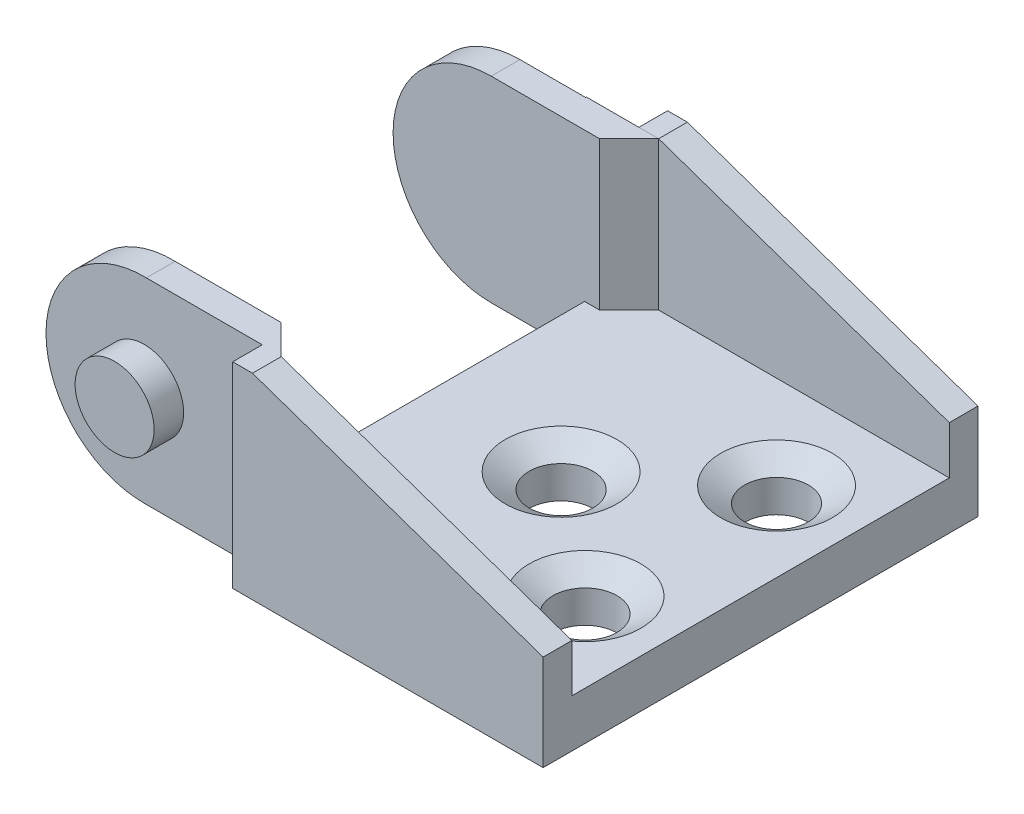
SolidWorks part; units mm, degrees
ref_plane "Front Plane" through (0, 0, 0) normal (0, 0, 1) x (1, 0, 0)
ref_plane "Top Plane" through (0, 0, 0) normal (0, 1, 0) x (1, 0, 0)
ref_plane "Right Plane" through (0, 0, 0) normal (1, 0, 0) x (0, 0, -1)
sketch "Sketch1" plane through (0, 0, 0) normal (1, 0, 0) x (0, 0, -1)
  line L0 (0, 12.3) -> (0, 0)
  line L1 (0, 0) -> (27.25, 0)
  line L2 (27.25, 0) -> (27.25, 12.3)
  line L3 (27.25, 12.3) -> (25.45, 12.3)
  line L4 (25.45, 12.3) -> (25.45, 3)
  line L5 (25.45, 3) -> (1.8, 3)
  line L6 (1.8, 3) -> (1.8, 12.3)
  line L7 (1.8, 12.3) -> (0, 12.3)
  dimension "D1" = 27.25
  dimension "D2" = 1.8
  dimension "D4" = 12.3
extrude "ProfileBoss-Extrude1" add sketch "Sketch1" along normal blind 33
sketch "Sketch2" plane through (0, 0, 0) normal (0, 0, 1) x (1, 0, 0)
  line L1 (14.7896, 12.3) -> (33, 6)
  line L2 (33, 12.3) -> (0, 12.3) construction
  line L3 (0, 12.3) -> (0, 0) construction
  line L4 (33, 12.3) -> (33, 0) construction
  line L5 (33, 6) -> (33, 0)
  line L6 (33, 0) -> (6.15, 0)
  line L7 (33, 0) -> (0, 0) construction
  line L8 (6.2896, 12.2984) -> (14.7896, 12.3)
  arc A0 (6.2896, 12.2984) -> (6.15, 0) centre (6.15, 6.15) ccw
  dimension "D1" = 12.3
  dimension "D4" = 6
  dimension "D2" = 8.5
extrude "SideProfileCut-Extrude1" cut sketch "Sketch2" against normal through all flip side to cut
sketch "Sketch3" plane through (0, 3, 0) normal (0, 1, 0) x (1, 0, 0)
  line L0 (0.868, 25.45) -> (12, 25.45)
  line L4 (12, 25.45) -> (12, 1.8)
  line L8 (12, 1.8) -> (0.868, 1.8)
  line L9 (0.868, 1.8) -> (0.868, 25.45)
  line L10 (33, 25.45) -> (33, 1.8) construction
  line L11 (14.7896, 25.45) -> (33, 25.45) construction
  dimension "D1" = 21
extrude "BottomCut-Extrude2" cut sketch "Sketch3" against normal through all
sketch "DragLinkMountHolesSketch4" plane through (0, 3, 0) normal (0, 1, 0) x (1, 0, 0)
  line L0 (33, 25.45) -> (33, 1.8) construction
  line L1 (33, 0) -> (14.7896, 0) construction
  circle A0 centre (28, 19.625) radius 2
  circle A1 centre (28, 7.625) radius 2
  circle A2 centre (20.5, 13.625) radius 2
  dimension "D6" = 4
  dimension "D2" = 6
  dimension "D3" = 7.5
  dimension "D4" = 5
  dimension "D5" = 13.625
extrude "DragLinkMountHolesCut-Extrude3" cut sketch "DragLinkMountHolesSketch4" against normal through all
chamfer "Chamfer1" distance 1.5 angle 33 3 edges at (28, 3, -5.625) (28, 3, -17.625) (20.5, 3, -11.625) first distance on face at (28, 3, -17.625)
sketch "Sketch11" plane through (0, 0, -25.45) normal (0, 0, 1) x (1, 0, 0)
  line L0 (14.7896, 12.3) -> (6.15, 12.3)
  line L1 (14.7896, 12.3) -> (14.7896, 0)
  line L2 (14.7896, 0) -> (6.15, 0)
  arc A0 (6.15, 12.3) -> (6.15, 0) centre (6.15, 6.15) ccw
  arc A1 (6.2896, 12.2984) -> (6.15, 0) centre (6.15, 6.15) ccw construction
extrude "RightInnerBoss-Extrude3" add sketch "Sketch11" along normal blind 1.85
sketch "Sketch12" plane through (0, 0, -1.8) normal (0, 0, -1) x (-1, 0, 0)
  line L0 (-14.7896, 12.3) -> (-6.2896, 12.2984)
  line L1 (-6.15, 0) -> (-14.7896, 0)
  line L2 (-14.7896, 0) -> (-14.7896, 12.3)
  arc A0 (-6.15, 0) -> (-6.2896, 12.2984) centre (-6.15, 6.15) ccw
  arc A1 (-6.15, 0) -> (-6.2896, 12.2984) centre (-6.15, 6.15) ccw construction
extrude "LeftInnerBoss-Extrude4" add sketch "Sketch12" along normal blind 1.85
sketch "RightOuterCircleSketch7" plane through (0, 0, -27.25) normal (0, 0, -1) x (-1, 0, 0)
  line L1 (-13.55, 12.2998) -> (-10.2668, 12.2992)
  line L2 (-14.7896, 12.3) -> (-6.2896, 12.2984) construction
  line L3 (-33, 0) -> (-6.15, 0) construction
  line L4 (-10.2655, 0) -> (-13.55, 0)
  line L5 (-13.55, 0) -> (-13.55, 12.2998)
  arc A0 (-10.2655, 0) -> (-10.2668, 12.2992) centre (-6.15, 6.15) ccw
  arc A1 (-6.15, 0) -> (-6.2896, 12.2984) centre (-6.15, 6.15) ccw construction
  circle A2 centre (-6.15, 6.15) radius 2.5
  dimension "D2" = 14.8
  dimension "D3" = 3.2832
extrude "RightOuterCircleCut-Extrude4" cut sketch "RightOuterCircleSketch7" against normal blind 1.85
sketch "Sketch8" plane through (0, 0, 0) normal (0, 0, 1) x (1, 0, 0)
  line L1 (13.55, 12.2998) -> (10.2668, 12.2992)
  line L2 (14.7896, 12.3) -> (6.2896, 12.2984) construction
  line L3 (33, 0) -> (6.15, 0) construction
  line L4 (10.2655, 0) -> (13.5487, 0)
  line L5 (13.55, 12.2998) -> (13.5487, 0)
  arc A0 (10.2668, 12.2992) -> (10.2655, 0) centre (6.15, 6.15) ccw
  circle A2 centre (6.15, 6.15) radius 2.475
  arc A3 (6.2896, 12.2984) -> (6.15, 0) centre (6.15, 6.15) ccw construction
  dimension "D1" = 4.95
  dimension "D3" = 14.8
  dimension "D2" = 3.2832
extrude "LeftOuterCircleCut-Extrude5" cut sketch "Sketch8" against normal blind 1.85
chamfer "Chamfer2" distance 1.85 angle 45 2 edges at (14.7896, 7.65, -23.6) (14.7896, 7.65, -3.65)
equation "\"DragLinkDepth\"=12.3"
equation "\"D4@Sketch1\"=\"DragLinkDepth\""
equation "\"DragLinkSideWallThickness\"= 1.8mm"
equation "\"D2@Sketch1\"=\"DragLinkSideWallThickness\""
equation "\"D5@DragLinkMountHolesSketch4\" = \"DragLinkHeight\" / 2"
equation "\"DragLinkHeight\"= 27.25"
equation "\"D1@Sketch1\"=\"DragLinkHeight\""
equation "\"DragLinkWidth\"=33"
equation "\"D1@ProfileBoss-Extrude1\"=\"DragLinkWidth\""
equation "\"DragLinkMountHoleDiameter\"=4"
equation "\"MiddleSideHole\"= 5mm"
equation "\"OutsideCircleDiameter\"=14.27"
equation "\"D1@Sketch2\"=\"DragLinkDepth\""
equation "\"InsideCircleDepth\"=1.85"
equation "\"D1@RightOuterCircleSketch7\" = \"MiddleSideHole\""
equation "\"D1@RightOuterCircleCut-Extrude4\"=\"InsideCircleDepth\""
equation "\"D1@Sketch8\"=\"MiddleSideHole\" - .05"
equation "\"D1@LeftOuterCircleCut-Extrude5\" = \"InsideCircleDepth\""
equation "\"D2@Sketch2\"=\"DragLinkDepth\"/2 + 2.35mm"
equation "\"D1@RightInnerBoss-Extrude3\" = \"InsideCircleDepth\""
equation "\"D1@LeftInnerBoss-Extrude4\" = \"InsideCircleDepth\""
equation "\"D2@RightOuterCircleSketch7\"=\"DragLinkDepth\" + 2.5mm"
equation "\"D1@Chamfer2\"=\"InsideCircleDepth\""
